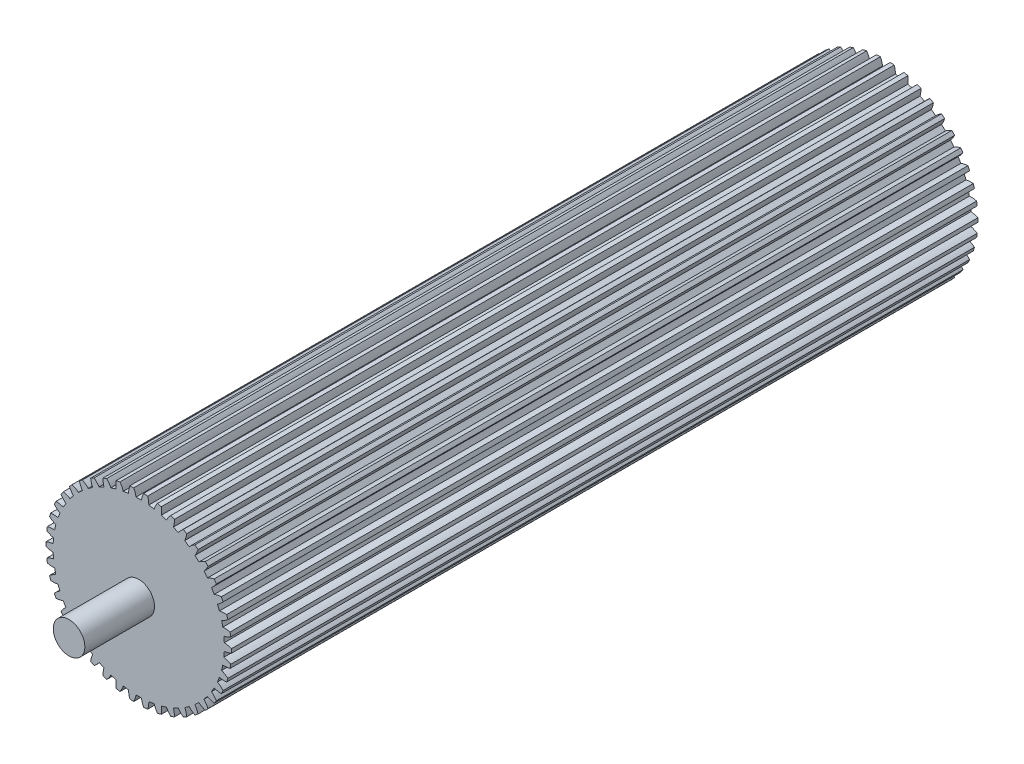
SolidWorks part; units mm, degrees
material "Brass"
ref_plane "Front Plane" through (0, 0, 0) normal (0, 0, 1) x (1, 0, 0)
ref_plane "Top Plane" through (0, 0, 0) normal (0, 1, 0) x (1, 0, 0)
ref_plane "Right Plane" through (0, 0, 0) normal (1, 0, 0) x (0, 0, -1)
sketch "Sketch1" plane through (0, 0, 0) normal (0, 0, 1) x (1, 0, 0)
  circle A0 centre (0, 0) radius 18.6267
  dimension "D1" = 37.2533
extrude "Boss-Extrude1" add sketch "Sketch1" along normal blind 150
sketch "Sketch2" plane through (0, 0, 0) normal (0, 0, 1) x (1, 0, 0)
  spline S0 degree 4 poles (17.1978, 0.739) (17.2039, 0.7392) (17.2154, 0.7393) (17.2343, 0.7391) (17.2715, 0.7379) (17.3137, 0.7353) (17.3614, 0.7312) (17.4127, 0.7257) (17.4566, 0.7203) (17.5005, 0.7141) (17.5443, 0.7075) (17.5973, 0.6986) (17.661, 0.6871) (17.7355, 0.6721) (17.8202, 0.6533) (17.9066, 0.6324) (17.9918, 0.6103) (18.078, 0.5862) (18.1615, 0.5616) (18.2484, 0.5343) (18.3286, 0.5082) (18.4188, 0.4769) (18.4915, 0.451) (18.5877, 0.4148) (18.6446, 0.3928) (18.7113, 0.3663) (18.7409, 0.3541) (18.7591, 0.3466) knots 0 0 0 0 0 0.015084 0.028532 0.04661 0.092111 0.119476 0.146842 0.174209 0.201575 0.228941 0.256307 0.307035 0.361767 0.4165 0.471232 0.525964 0.580697 0.635429 0.690161 0.744894 0.799626 0.854358 0.909091 0.954545 1 1 1 1 1 construction
  spline S1 degree 4 poles (17.1978, 0.739) (17.2039, 0.7392) (17.2154, 0.7393) (17.2343, 0.7391) (17.2715, 0.7379) (17.3137, 0.7353) (17.3614, 0.7312) (17.4127, 0.7257) (17.4566, 0.7203) (17.5005, 0.7141) (17.5443, 0.7075) (17.5973, 0.6986) (17.661, 0.6871) (17.7355, 0.6721) (17.8202, 0.6533) (17.9066, 0.6324) (17.9918, 0.6103) (18.078, 0.5862) (18.1615, 0.5616) (18.2484, 0.5343) (18.3286, 0.5082) (18.4188, 0.4769) (18.4915, 0.451) (18.5669, 0.4227) (18.6036, 0.4086) (18.6223, 0.4013) knots 0 0 0 0 0 0.015084 0.028532 0.04661 0.092111 0.119476 0.146842 0.174209 0.201575 0.228941 0.256307 0.307035 0.361767 0.4165 0.471232 0.525964 0.580697 0.635429 0.690161 0.744894 0.799626 0.854358 0.909091 0.909091 0.909091 0.909091 0.909091
  spline S2 degree 4 poles (17.1159, 1.8324) (17.1219, 1.8331) (17.1333, 1.8348) (17.152, 1.8378) (17.1886, 1.8446) (17.2299, 1.8534) (17.2765, 1.8645) (17.3264, 1.8776) (17.369, 1.8896) (17.4115, 1.9022) (17.4538, 1.9153) (17.5049, 1.9319) (17.5661, 1.9529) (17.6376, 1.9788) (17.7185, 2.0099) (17.8009, 2.0435) (17.8818, 2.0781) (17.9634, 2.1148) (18.0423, 2.1515) (18.1242, 2.1915) (18.1997, 2.2293) (18.2841, 2.2736) (18.3522, 2.31) (18.442, 2.3602) (18.4949, 2.3904) (18.5569, 2.4266) (18.5843, 2.4431) (18.6013, 2.4532) knots 0 0 0 0 0 0.015084 0.028532 0.04661 0.092111 0.119476 0.146842 0.174209 0.201575 0.228941 0.256307 0.307035 0.361767 0.4165 0.471232 0.525964 0.580697 0.635429 0.690161 0.744894 0.799626 0.854358 0.909091 0.954545 1 1 1 1 1 construction
  spline S3 degree 4 poles (17.1159, 1.8324) (17.1219, 1.8331) (17.1333, 1.8348) (17.152, 1.8378) (17.1886, 1.8446) (17.2299, 1.8534) (17.2765, 1.8645) (17.3264, 1.8776) (17.369, 1.8896) (17.4115, 1.9022) (17.4538, 1.9153) (17.5049, 1.9319) (17.5661, 1.9529) (17.6376, 1.9788) (17.7185, 2.0099) (17.8009, 2.0435) (17.8818, 2.0781) (17.9634, 2.1148) (18.0423, 2.1515) (18.1242, 2.1915) (18.1997, 2.2293) (18.2841, 2.2736) (18.3522, 2.31) (18.4225, 2.3493) (18.4567, 2.3687) (18.4742, 2.3787) knots 0 0 0 0 0 0.015084 0.028532 0.04661 0.092111 0.119476 0.146842 0.174209 0.201575 0.228941 0.256307 0.307035 0.361767 0.4165 0.471232 0.525964 0.580697 0.635429 0.690161 0.744894 0.799626 0.854358 0.909091 0.909091 0.909091 0.909091 0.909091
  spline S4 degree 1 poles (17.1159, 1.8324) (17.1978, 0.739) knots 0 0 1 1 construction
  spline S5 degree 1 poles (17.1159, 1.8324) (17.1978, 0.739) knots 0 0 1 1
  spline S6 degree 1 poles (18.6223, 0.4013) (59.9861, 1.2927) knots 0 0 1 1 construction
  spline S7 degree 1 poles (18.6223, 0.4013) (59.9861, 1.2927) knots 0 0 1 1
  spline S8 degree 4 poles (59.9965, 0.6495) (59.996, 0.6954) (59.9948, 0.7841) (59.9935, 0.9041) (59.9876, 1.2291) (59.9845, 1.3714) (59.9739, 1.7905) (59.9657, 2.0284) (59.9537, 2.3723) (59.9415, 2.6523) (59.9269, 2.9708) (59.9113, 3.2659) (59.8938, 3.5749) (59.875, 3.8756) (59.8545, 4.1808) (59.8325, 4.4838) (59.8091, 4.7868) (59.7838, 5.0915) (59.7577, 5.3917) (59.7289, 5.6999) (59.7003, 5.9941) (59.6673, 6.3111) (59.6376, 6.5899) (59.5983, 6.9317) (59.5709, 7.1681) (59.5189, 7.5842) (59.5007, 7.7253) (59.4582, 8.0476) (59.4416, 8.1664) (59.4295, 8.2543) (59.4232, 8.2997) knots 0 0 0 0 0 0.020959 0.041918 0.083333 0.123016 0.162698 0.202381 0.242063 0.281746 0.321429 0.361111 0.400794 0.440476 0.480159 0.519841 0.559524 0.599206 0.638889 0.678571 0.718254 0.757937 0.797619 0.837302 0.876984 0.916667 0.958082 0.979041 1 1 1 1 1 construction
  spline S9 degree 4 poles (59.9861, 1.2927) (59.9847, 1.3561) (59.9818, 1.4796) (59.9739, 1.7905) (59.9657, 2.0284) (59.9537, 2.3723) (59.9415, 2.6523) (59.9269, 2.9708) (59.9113, 3.2659) (59.8938, 3.5749) (59.875, 3.8756) (59.8545, 4.1808) (59.8325, 4.4838) (59.8091, 4.7868) (59.7838, 5.0915) (59.7577, 5.3917) (59.7289, 5.6999) (59.7003, 5.9941) (59.6673, 6.3111) (59.6376, 6.5899) (59.5983, 6.9317) (59.5709, 7.1681) (59.5324, 7.4768) (59.5168, 7.5993) (59.5087, 7.6622) knots 0.083333 0.083333 0.083333 0.083333 0.083333 0.123016 0.162698 0.202381 0.242063 0.281746 0.321429 0.361111 0.400794 0.440476 0.480159 0.519841 0.559524 0.599206 0.638889 0.678571 0.718254 0.757937 0.797619 0.837302 0.876984 0.916667 0.916667 0.916667 0.916667 0.916667
  spline S10 degree 1 poles (59.5087, 7.6622) (18.4742, 2.3787) knots 0 0 1 1 construction
  spline S11 degree 1 poles (59.5087, 7.6622) (18.4742, 2.3787) knots 0 0 1 1
extrude "Cut-Extrude2" cut sketch "Sketch2" against normal blind 151 and the other way blind 151
ref_axis "Axis1" through (0, 0, -16.6) along (0, 0, 1)
pattern_circular "CirPattern1" count 42 over 360 about axis through (0, 0, -16.6) along (0, 0, 1) of "Cut-Extrude2"
sketch "Sketch3" plane through (0, 0, 0) normal (0, 0, 1) x (1, 0, 0)
  circle A0 centre (0, 0) radius 3.175
  dimension "D1" = 6.35
extrude "Boss-Extrude2" add sketch "Sketch3" against normal blind 8 from offset 0 offset against normal yes
sketch "Sketch4" plane through (0, 0, 0) normal (0, 0, 1) x (1, 0, 0)
  circle A0 centre (0, 0) radius 3.175
  dimension "D1" = 6.35
extrude "Boss-Extrude3" add sketch "Sketch4" along normal blind 14 from offset 150
